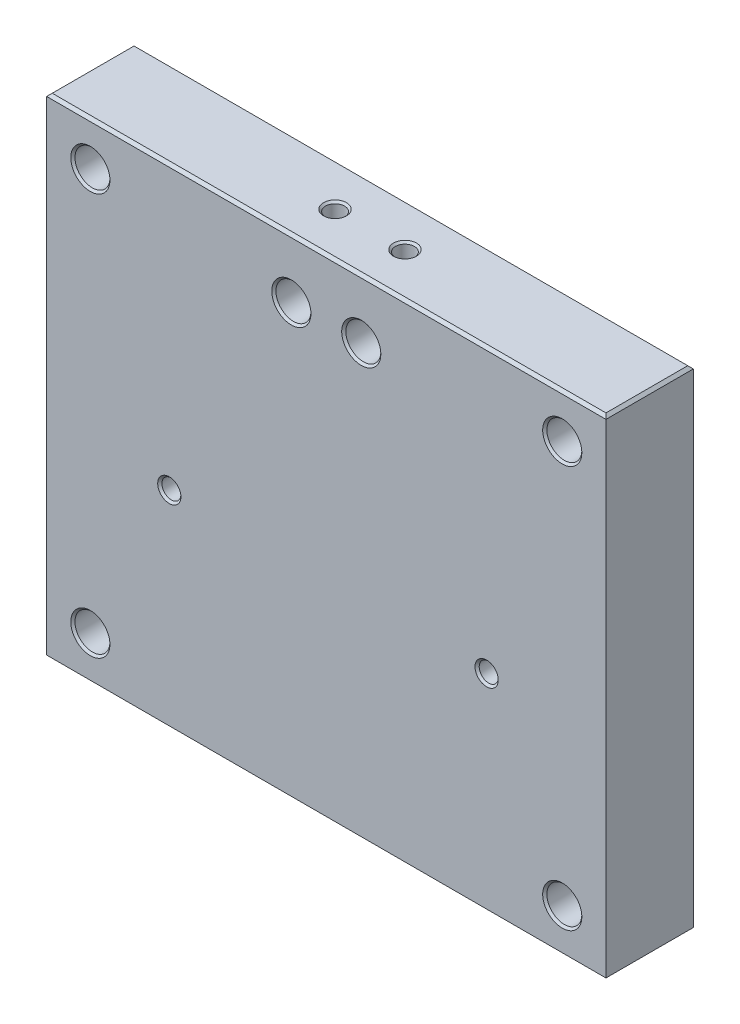
SolidWorks part; units mm, degrees
material "Brass"
ref_plane "Front Plane" through (0, 0, 0) normal (0, 0, 1) x (1, 0, 0)
ref_plane "Top Plane" through (0, 0, 0) normal (0, 1, 0) x (1, 0, 0)
ref_plane "Right Plane" through (0, 0, 0) normal (1, 0, 0) x (0, 0, -1)
sketch "Sketch1" plane through (0, 0, 0) normal (0, 0, 1) x (1, 0, 0)
  line L1 (0, 0) -> (-101.6, 0)
  line L2 (0, 0) -> (0, 88.9)
  line L3 (0, 88.9) -> (-101.6, 88.9)
  line L4 (-101.6, 0) -> (-101.6, 88.9)
  dimension "D1" = 101.6
  dimension "D2" = 88.9
extrude "Boss-Extrude1" add sketch "Sketch1" along normal blind 15.875
sketch "Sketch5" plane through (0, 88.9, 0) normal (0, 1, 0) x (1, 0, 0)
  line L0 (-101.6, -7.9375) -> (0, -7.9375) construction
  line L1 (-101.6, -15.875) -> (-101.6, 0) construction
  line L2 (0, -15.875) -> (0, 0) construction
  line L3 (-57.15, -7.9375) -> (-44.45, -7.9375)
  point P8 (-50.8, -7.9375)
  dimension "D1" = 12.7
hole_wizard "#8-32 Tapped Hole1" positions "Sketch6" profile "Sketch8" tap size "#8-32" standard "ANSI Inch"
sketch "Sketch6" plane through (0, 88.9, 0) normal (0, 1, 0) x (1, 0, 0)
  point P0 (-44.45, -7.9375)
  point P3 (-57.15, -7.9375)
sketch "Sketch8" plane through (-44.45, 88.9, 7.9375) normal (1, 0, 0) x (0, 0, 1)
  line L0 (0, 0) -> (0, 10.6898)
  line L1 (0, 10.6898) -> (1.7272, 9.652)
  line L2 (1.7272, 9.652) -> (1.7272, 0.3556)
  line L3 (1.7272, 0.3556) -> (2.0828, 0)
  line L5 (2.0828, 0) -> (0, 0)
  line L6 (-1.7272, 0.3556) -> (-2.0828, 0) construction
  line L10 (0, 10.6898) -> (-1.7272, 9.652) construction
  line L11 (0, -6.35) -> (0, 107.95) construction
  dimension "Tap Drill Dia." = 3.4544
  dimension "Tap Drill Depth" = 9.652
  dimension "Near C'Sink Dia." = 4.1656
  dimension "Near C'Sink Angle" = 90
  dimension "Drill Angle" = 118
cosmetic thread "Hole Thread1" parameters "D1"=9.2511, "D2"=4.1656
cosmetic thread "Hole Thread2" parameters "D1"=9.2511, "D2"=4.1656
hole_wizard "1/4 (0.25) Diameter Hole1" positions "Sketch11" profile "Sketch12" hole size "1/4" standard "ANSI Inch"
sketch "Sketch11" plane through (0, 0, 15.875) normal (0, 0, 1) x (1, 0, 0)
  line L0 (-44.45, 78.2102) -> (-42.7228, 79.248) construction
  line L1 (-57.15, 78.2102) -> (-55.4228, 79.248) construction
  line L2 (-44.45, 78.2102) -> (-42.7228, 79.248)
  line L3 (-57.15, 78.2102) -> (-55.4228, 79.248)
  point P1 (-44.45, 78.2102)
  point P3 (-57.15, 78.2102)
sketch "Sketch12" plane through (-44.45, 78.2102, 15.875) normal (1, 0, 0) x (0, -1, 0)
  line L0 (0, 0) -> (0, 27.3077)
  line L1 (0, 27.3077) -> (3.175, 25.4)
  line L2 (3.175, 25.4) -> (3.175, 0)
  line L5 (3.175, 0) -> (0, 0)
  line L10 (0, 27.3077) -> (-3.175, 25.4) construction
  line L11 (0, -6.35) -> (0, 107.95) construction
  dimension "Hole Dia." = 6.35
  dimension "Hole Depth" = 25.4
  dimension "Drill Angle" = 118
sketch "Sketch13" plane through (0, 0, 15.875) normal (0, 0, 1) x (1, 0, 0)
  line L8 (-6.35, 6.35) -> (-6.35, 82.55)
  line L9 (-6.35, 82.55) -> (-95.25, 82.55)
  line L10 (-95.25, 82.55) -> (-95.25, 6.35)
  line L11 (-95.25, 6.35) -> (-6.35, 6.35)
  line L12 (-6.35, 6.35) -> (-6.35, 82.55)
  line L13 (-6.35, 82.55) -> (-95.25, 82.55)
  line L14 (-95.25, 82.55) -> (-95.25, 6.35)
  line L15 (-95.25, 6.35) -> (-6.35, 6.35)
  dimension "D1" = 6.35
sketch "Sketch17" plane through (0, 0, 15.875) normal (0, 0, 1) x (1, 0, 0)
  line L0 (-82.55, 12.7) -> (-19.05, 12.7)
  line L1 (-82.55, 12.7) -> (-101.6, 12.7)
  line L2 (-101.6, 88.9) -> (-101.6, 0) construction
  line L3 (-19.05, 12.7) -> (0, 12.7)
  line L4 (0, 0) -> (0, 88.9) construction
  line L5 (-101.6, 0) -> (0, 0) construction
  dimension "D1" = 63.5
  dimension "D2" = 12.7
hole_wizard "#8-32 Tapped Hole2" positions "Sketch21" profile "Sketch22" tap size "#8-32" standard "ANSI Inch" end condition through all
sketch "Sketch21" plane through (0, 0, 0) normal (0, 0, -1) x (-1, 0, 0)
  line L9 (5.8, 8.89) -> (95.8, 8.89)
  line L10 (5.8, 66.294) -> (5.8, 8.89)
  line L11 (95.8, 66.294) -> (5.8, 66.294)
  line L12 (95.8, 8.89) -> (95.8, 66.294)
  line L13 (5.8, 8.89) -> (95.8, 8.89)
  line L14 (5.8, 66.294) -> (5.8, 8.89)
  line L15 (95.8, 66.294) -> (5.8, 66.294)
  line L16 (95.8, 8.89) -> (95.8, 66.294)
  circle A4 centre (21.675, 37.592) radius 2.2479
  circle A5 centre (21.675, 37.592) radius 2.2479
  circle A8 centre (79.3203, 37.592) radius 2.2479
  circle A9 centre (79.3203, 37.592) radius 2.2479
  point P53 (79.3203, 37.592)
  point P56 (21.675, 37.592)
  dimension "D1" = 0
  dimension "D2" = 0
  dimension "D3" = 0
sketch "Sketch22" plane through (-21.675, 37.592, 0) normal (1, 0, 0) x (0, 1, 0)
  line L0 (0, 0) -> (0, 15.875)
  line L1 (0, 15.875) -> (1.7272, 15.875)
  line L2 (1.7272, 15.875) -> (1.7272, 0)
  line L5 (1.7272, 0) -> (0, 0)
  line L11 (0, -6.35) -> (0, 107.95) construction
  dimension "Thru Tap Drill Dia." = 3.4544
  dimension "Thru Tap Drill Depth" = 15.875
cosmetic thread "Hole Thread7" parameters "D2"=4.1656
cosmetic thread "Hole Thread8" parameters "D2"=4.1656
hole_wizard "#13 (0.185) Diameter Hole1" positions "Sketch25" profile "Sketch26" hole size "#13" standard "ANSI Inch"
sketch "Sketch25" plane through (0, 0, 0) normal (0, -1, 0) x (-1, 0, 0)
  line L0 (76.2, -7.9375) -> (25.4, -7.9375)
  line L2 (0, -15.875) -> (0, 0) construction
  line L3 (101.6, -15.875) -> (101.6, 0) construction
  line L4 (76.2, -7.9375) -> (101.6, -7.9375) construction
  line L6 (25.4, -7.9375) -> (0, -7.9375) construction
  point P1 (76.2, -7.9375)
  point P2 (25.4, -7.9375)
  point P6 (0, -7.9375)
  dimension "D1" = 50.8
sketch "Sketch26" plane through (-76.2, 0, 7.9375) normal (1, 0, 0) x (0, 0, -1)
  line L0 (0, 0) -> (0, 23.6367)
  line L1 (0, 23.6367) -> (2.3495, 22.225)
  line L2 (2.3495, 22.225) -> (2.3495, 0)
  line L5 (2.3495, 0) -> (0, 0)
  line L10 (0, 23.6367) -> (-2.3495, 22.225) construction
  line L11 (0, -6.35) -> (0, 107.95) construction
  dimension "Hole Dia." = 4.699
  dimension "Hole Depth" = 22.225
  dimension "Drill Angle" = 118
hole_wizard "Hole1" positions "Sketch27" profile "Sketch29" legacy end condition through all
sketch "Sketch27" plane through (0, 0, 0) normal (0, 0, 1) x (1, 0, 0)
  line L1 (-93.6625, 80.9625) -> (-7.9375, 80.9625)
  line L2 (-93.6625, 80.9625) -> (-93.6625, 7.9375)
  line L3 (-93.6625, 7.9375) -> (-7.9375, 7.9375)
  line L4 (-7.9375, 80.9625) -> (-7.9375, 7.9375)
  line L5 (-93.6625, 80.9625) -> (-7.9375, 7.9375) construction
  line L6 (-93.6625, 7.9375) -> (-7.9375, 80.9625) construction
  line L7 (-101.6, 88.9) -> (0, 0) construction
  line L9 (-93.6625, 44.45) -> (-101.6, 44.45) construction
  line L10 (-101.6, 88.9) -> (-101.6, 0) construction
  line L12 (-50.8, 7.9375) -> (-50.8, 0) construction
  line L14 (-101.6, 0) -> (0, 0) construction
  point P2 (-7.9375, 7.9375)
  point P5 (-93.6625, 80.9625)
  point P6 (-93.6625, 7.9375)
  point P7 (-7.9375, 80.9625)
  point P68 (0, 0)
  point P69 (0, 0)
  dimension "D1" = 7.9375
sketch "Sketch29" plane through (-7.9375, 7.9375, 0) normal (1, 0, 0) x (0, 1, 0)
  line L0 (0, 0) -> (0, 17.7827)
  line L1 (0, 17.7827) -> (3.175, 15.875)
  line L2 (3.175, 15.875) -> (3.175, 9.525)
  line L3 (3.175, 9.525) -> (4.7625, 9.525)
  line L4 (4.7625, 0) -> (0, 0)
  line L5 (0, -11.3109) -> (0, 121.1557) construction
  line L6 (0, 17.7827) -> (-3.175, 15.875) construction
  line L7 (4.7625, 9.525) -> (4.7625, 0)
  dimension "Depth" = 15.875
  dimension "Drill Angle" = 118
  dimension "Diameter" = 6.35
  dimension "C-Bore Diameter" = 9.525
  dimension "C-Bore Depth" = 9.525
chamfer "Chamfer1" distance 0.508 angle 45 8 edges at (-101.6, 0, 7.9375) (-50.8, 0, 15.875) (-50.8, 0, 0) (0, 0, 7.9375) (0, 88.9, 7.9375) (-50.8, 88.9, 0) (-50.8, 88.9, 15.875) (-101.6, 88.9, 7.9375)
chamfer "Chamfer2" distance 0.381 angle 45 16 edges at (-11.1125, 7.9375, 15.875) (-96.8375, 7.9375, 15.875) (-81.0475, 37.592, 15.875) (-23.4022, 37.592, 15.875) (-96.8375, 80.9625, 15.875) (-53.975, 78.2102, 15.875) (-41.275, 78.2102, 15.875) (-11.1125, 80.9625, 15.875) (-12.7, 80.9625, 0) (-12.7, 7.9375, 0) (-23.4022, 37.592, 0) (-81.0475, 37.592, 0) (-41.275, 78.2102, 0) (-53.975, 78.2102, 0) (-98.425, 80.9625, 0) (-98.425, 7.9375, 0)
